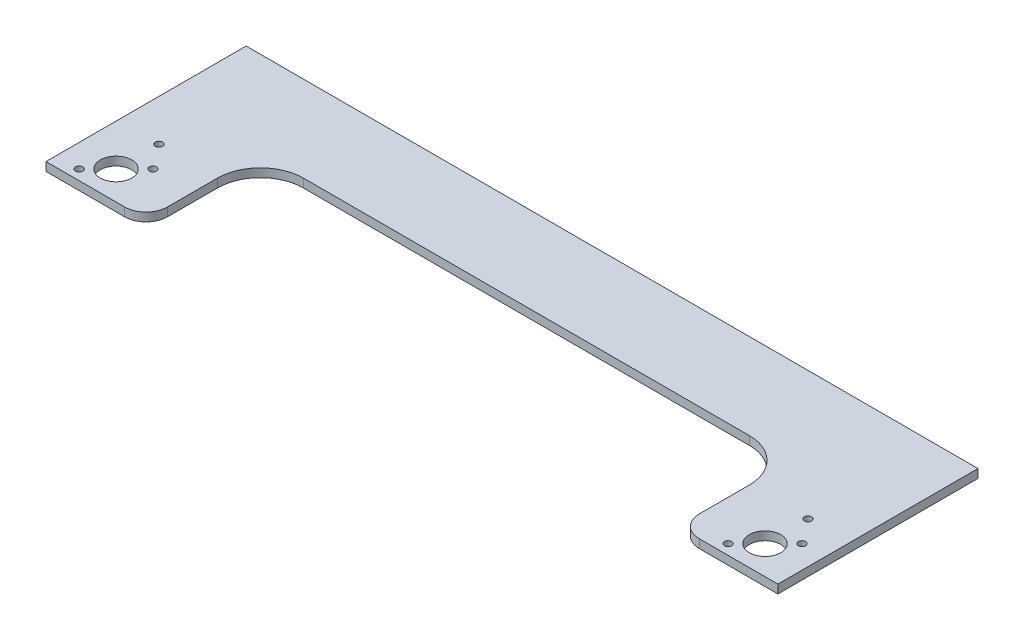
SolidWorks part; units mm, degrees
material "Клен"
ref_plane "Спереди" through (0, 0, 0) normal (0, 0, 1) x (1, 0, 0)
ref_plane "Сверху" through (0, 0, 0) normal (0, 1, 0) x (1, 0, 0)
ref_plane "Справа" through (0, 0, 0) normal (1, 0, 0) x (0, 0, -1)
sketch "Эскиз1" plane through (0, 0, 0) normal (0, 1, 0) x (1, 0, 0)
  line L0 (-322.2029, -260) -> (-322.2029, -120)
  line L5 (-322.2029, -120) -> (189.7971, -120)
  line L8 (119.7971, -245) -> (119.7971, -210)
  line L9 (89.7971, -180) -> (-222.2029, -180)
  line L10 (-252.2029, -210) -> (-252.2029, -245)
  line L11 (-267.2029, -260) -> (-322.2029, -260)
  line L13 (198.1199, -180) -> (-363.1649, -180) construction
  line L15 (-322.2029, 19.8148) -> (-322.2029, -120) construction
  line L17 (189.7971, -120) -> (189.7971, -260)
  line L18 (-66.2029, 248.8576) -> (-66.2029, -157.5742) construction
  line L20 (189.7971, -120) -> (189.7971, -260) construction
  line L21 (134.7971, -260) -> (189.7971, -260)
  arc A0 (-222.2029, -180) -> (-252.2029, -210) centre (-222.2029, -210) ccw
  arc A1 (119.7971, -210) -> (89.7971, -180) centre (89.7971, -210) ccw
  arc A2 (-252.2029, -245) -> (-267.2029, -260) centre (-267.2029, -245) cw
  arc A3 (134.7971, -260) -> (119.7971, -245) centre (134.7971, -245) cw
  circle A6 centre (-293.2029, -210) radius 2.55
  circle A8 centre (160.7971, -210) radius 2.55
  point P24 (-373.8346, -236.3372)
  dimension "D4" = 30
  dimension "D5" = 30
  dimension "D6" = 15
  dimension "D7" = 15
  dimension "D2" = 5.1
  dimension "D3" = 70
extrude "Бобышка-Вытянуть1" add sketch "Эскиз1" along normal blind 6
sketch "Эскиз7" plane through (0, 0, 0) normal (0, 1, 0) x (1, 0, 0)
  circle A1 centre (-293.2029, -240) radius 11
  circle A2 centre (-280.2982, -227.0953) radius 2.55
  circle A3 centre (-306.1076, -252.9047) radius 2.55
  dimension "D1" = 22
  dimension "D2" = 5.1
  dimension "D3" = 5.1
extrude "Вырез-Вытянуть1" cut sketch "Эскиз7" against normal blind 5 and the other way blind 14
sketch "Эскиз8" plane through (0, 0, 0) normal (0, 1, 0) x (1, 0, 0)
  circle A0 centre (160.7971, -240) radius 11
  circle A1 centre (147.8924, -252.9047) radius 2.55
  circle A2 centre (173.7018, -227.0953) radius 2.55
  dimension "D1" = 22
  dimension "D2" = 5.1
  dimension "D3" = 5.1
extrude "Вырез-Вытянуть2" cut sketch "Эскиз8" against normal blind 5 and the other way blind 11
equation "\"D3@Эскиз7\"=\"D2@Эскиз7\""
equation "\"D3@Эскиз8\"=\"D2@Эскиз8\""
